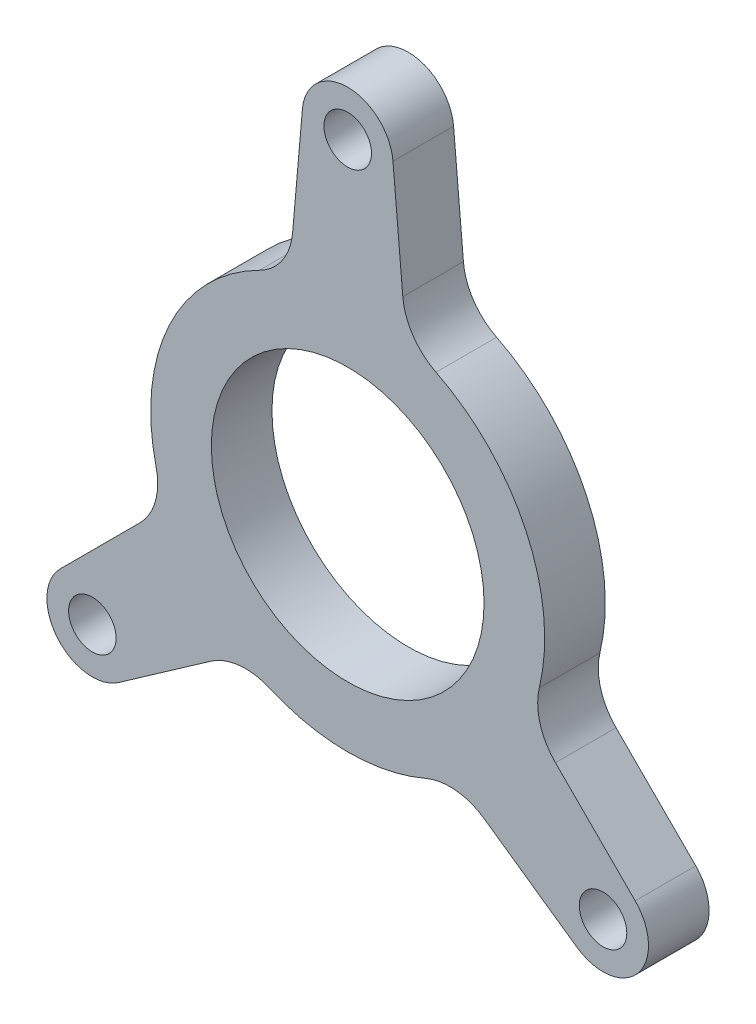
SolidWorks part; units mm, degrees
material "6061-T6 (SS)"
ref_plane "Front Plane" through (0, 0, 0) normal (0, 0, 1) x (1, 0, 0)
ref_plane "Top Plane" through (0, 0, 0) normal (0, 1, 0) x (1, 0, 0)
ref_plane "Right Plane" through (0, 0, 0) normal (1, 0, 0) x (0, 0, -1)
sketch "Sketch1" plane through (0, 0, 0) normal (0, 0, 1) x (1, 0, 0)
  line L0 (0, 0) -> (0, 34.925) construction
  line L1 (0, 0) -> (26.7541, -22.4494) construction
  line L2 (0, 0) -> (-26.7541, -22.4494) construction
  line L3 (-4.7444, 35.3401) -> (-6.1117, 19.7118)
  line L4 (4.7444, 35.3401) -> (6.1117, 19.7118)
  line L5 (30.1217, -19.0818) -> (19.0286, -7.9887)
  line L6 (24.0224, -26.3506) -> (11.1716, -17.3523)
  line L7 (-24.0224, -26.3506) -> (-11.1716, -17.3523)
  line L8 (-19.0286, -7.9887) -> (-30.1217, -19.0818)
  circle A0 centre (26.7541, -22.4494) radius 4.7625
  circle A1 centre (0, 34.925) radius 4.7625
  circle A2 centre (-26.7541, -22.4494) radius 4.7625
  circle A3 centre (26.7541, -22.4494) radius 2.4892
  circle A4 centre (-26.7541, -22.4494) radius 2.4892
  circle A5 centre (0, 34.925) radius 2.4892
  circle A6 centre (0, 0) radius 14.2875
  circle A7 centre (0, 0) radius 20.6375
  dimension "D1" = 9.525
  dimension "D4" = 4.9784
  dimension "D14" = 28.575
  dimension "D2" = 34.925
  dimension "D5" = 130
  dimension "D6" = 130
  dimension "D7" = 5
  dimension "D8" = 5
  dimension "D9" = 5
  dimension "D10" = 5
  dimension "D11" = 5
  dimension "D12" = 5
  dimension "D13" = 6.35
extrude "Boss-Extrude1" add sketch "Sketch1" along normal mid plane 6.35 contours A7 A6 | A7 L4 A1 L3 | A7 L6 A0 L5 | A7 L8 A2 L7 | A2 A4 | A1 A5 | A0 A3 region at (0, 25.7229, 0) region at (0, 39.5528, 0) region at (0, 20.0538, 0) region at (-19.7049, -16.5343, 0) region at (-24.9831, -18.1738, 0) region at (19.7049, -16.5343, 0) region at (31.0296, -20.6784, 0)
fillet "Fillet1" radius 6.35 6 edges at (19.0286, -7.9887, 0) (11.1716, -17.3523, 0) (-11.1716, -17.3523, 0) (-19.0286, -7.9887, 0) (-6.1117, 19.7118, 0) (6.1117, 19.7118, 0)
equation "\"D6@Sketch1\"=\"D5@Sketch1\""
